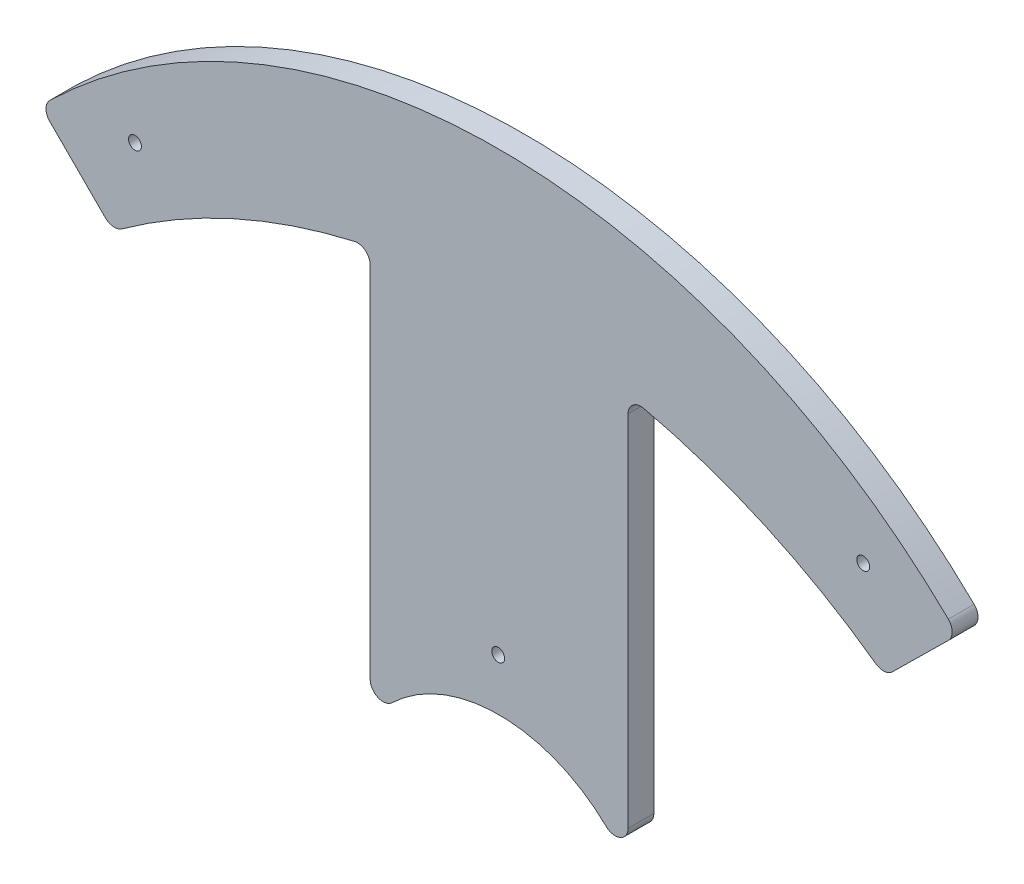
SolidWorks part; units mm, degrees
ref_plane "Front Plane" through (0, 0, 0) normal (0, 0, 1) x (1, 0, 0)
ref_plane "Top Plane" through (0, 0, 0) normal (0, 1, 0) x (1, 0, 0)
ref_plane "Right Plane" through (0, 0, 0) normal (1, 0, 0) x (0, 0, -1)
sketch "Sketch1" plane through (0, 0, 0) normal (0, 0, 1) x (1, 0, 0)
  line L0 (-39.5421, 82.9924) -> (-39.5421, 178.0088) construction
  line L2 (-14.5307, 146.0547) -> (-14.5307, 76.44)
  line L3 (-64.5405, 146.0546) -> (-64.5405, 76.4527)
  line L4 (-114.3623, 126.7922) -> (-114.571, 126.7922)
  line L5 (-127.4176, 140.8746) -> (-60.816, 74.2731) construction
  line L6 (-18.793, 74.6669) -> (48.3402, 140.859) construction
  line L7 (36.7347, 128.3614) -> (47.5955, 139.0699)
  line L10 (-115.9064, 128.31) -> (-126.6854, 139.089)
  arc A0 (33.5184, 128.113) -> (-11.4693, 148.4909) centre (-39.5353, 26.6824) ccw
  arc A1 (47.5827, 142.6428) -> (-126.66, 142.6496) centre (-39.5421, 53.0088) ccw
  arc A2 (-18.7627, 74.6372) -> (-60.3094, 74.6489) centre (-39.5421, 53.0088) ccw
  arc A3 (-14.5307, 76.44) -> (-18.7627, 74.6372) centre (-17.0307, 76.44) cw
  arc A4 (-64.5405, 76.4527) -> (-60.3094, 74.6489) centre (-62.0405, 76.4527) ccw
  arc A5 (-67.6018, 148.4908) -> (-112.6758, 128.0504) centre (-39.5353, 26.6824) ccw
  arc A6 (36.7347, 128.3614) -> (33.5184, 128.113) centre (34.9795, 130.1416) cw
  arc A7 (47.5955, 139.0699) -> (47.5827, 142.6428) centre (45.8402, 140.8501) ccw
  arc A8 (-126.6854, 139.089) -> (-126.66, 142.6496) centre (-124.9176, 140.8568) cw
  arc A9 (-115.9064, 128.31) -> (-112.6758, 128.0504) centre (-114.1386, 130.0778) ccw
  arc A10 (-11.4693, 148.4909) -> (-14.5307, 146.0547) centre (-12.0307, 146.0547) ccw
  arc A11 (-64.5405, 146.0546) -> (-67.6018, 148.4908) centre (-67.0405, 146.0546) ccw
  circle A13 centre (-110.1578, 143.7746) radius 1.25
  circle A14 centre (31.0735, 143.7746) radius 1.25
  circle A15 centre (-39.7176, 92.9924) radius 1.25
  point P9 (-42.8309, 76.2572)
  point P18 (-39.5421, 132.0448)
  point P21 (-114.3886, 126.7922)
  point P46 (-63.0209, 74.1529)
  point P51 (-16.0509, 74.14)
  point P56 (-39.5337, 83.0017)
  dimension "D1" = 125
  dimension "D2" = 125
  dimension "D4" = 15
  dimension "D7" = 2.5
  dimension "D10" = 2.5
  dimension "D12" = 2.5
  dimension "D15" = 45
  dimension "D9" = 2.5
  dimension "D3" = 10
  dimension "D16" = 46.97
extrude "Boss-Extrude1" add sketch "Sketch1" along normal blind 5 contours A11 L3 A4 A2 A3 L2 A10 A0 A6 L7 A7 A1 A8 L10 A9 A5 A15 A13 A14 region at (-39.5494, 137.1885, 0)
